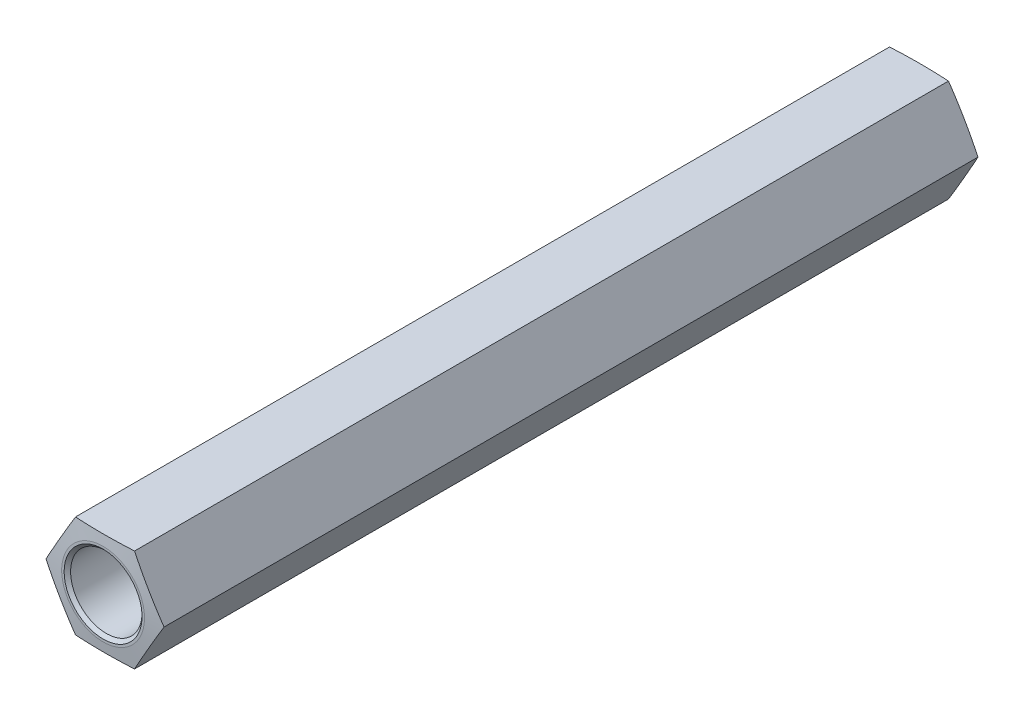
SolidWorks part; units mm, degrees
material "Plain Carbon Steel"
ref_plane "Front Plane" through (0, 0, 0) normal (0, 0, 1) x (1, 0, 0)
ref_plane "Top Plane" through (0, 0, 0) normal (0, 1, 0) x (1, 0, 0)
ref_plane "Right Plane" through (0, 0, 0) normal (1, 0, 0) x (0, 0, -1)
sketch "Sketch1" plane through (0, 0, 0) normal (0, 0, 1) x (1, 0, 0)
  line L0 (-3.6662, 0) -> (-1.8331, -3.175)
  line L1 (-1.8331, -3.175) -> (1.8331, -3.175)
  line L2 (1.8331, -3.175) -> (3.6662, 0)
  line L3 (3.6662, 0) -> (1.8331, 3.175)
  line L4 (1.8331, 3.175) -> (-1.8331, 3.175)
  line L5 (-1.8331, 3.175) -> (-3.6662, 0)
  line L6 (0, 3.175) -> (0, -3.175) construction
  line L7 (-2.7496, 1.5875) -> (0, 0) construction
  circle A0 centre (0, 0) radius 2.22
  point P2 (0, 0)
  dimension "D8" = 4.44
  dimension "D1" = 3.6662
  dimension "D2" = 3.6662
  dimension "D3" = 3.6662
  dimension "D4" = 3.175
  dimension "D5" = 6.35
  dimension "D6" = 7.3323
  dimension "D7" = 3.6662
extrude "Extrude1" add sketch "Sketch1" along normal mid plane 50.8
cosmetic thread "Cosmetic Thread1" parameters "D2"=5
chamfer "Chamfer1" distance 0.2 angle 45 2 edges at (2.22, 0, -25.4) (2.22, 0, 25.4)
ref_plane "Plane1" through (0, 0, 0) normal (0, 1, 0) x (-1, 0, 0)
sketch "Sketch2" plane through (0, 0, 0) normal (0, -1, 0) x (1, 0, 0)
  line L0 (-2.5727, -25.4) -> (-3.6662, -25.28)
  line L3 (-3.6662, -25.28) -> (-3.6662, -25.4)
  line L4 (-3.6662, -25.4) -> (-2.5727, -25.4)
  dimension "D1" = 1.0934
  dimension "D2" = 0.12
revolve "Cut-Revolve1" cut sketch "Sketch2" angle 360 about axis through (0, 0, 25.4) along (0, 0, -1)
mirror "Mirror1" about plane through (0, 0, 0) normal (0, 0, 1) of "Cut-Revolve1"
ref_axis "Axis1" through (0, 0, -28.7493) along (0, 0, 1)
ref_plane "Plane2" through (0, 0, 26.72) normal (0, 0, 1) x (1, 0, 0)
ref_plane "Plane3" through (0, 0, -26.72) normal (0, 0, 1) x (1, 0, 0)
